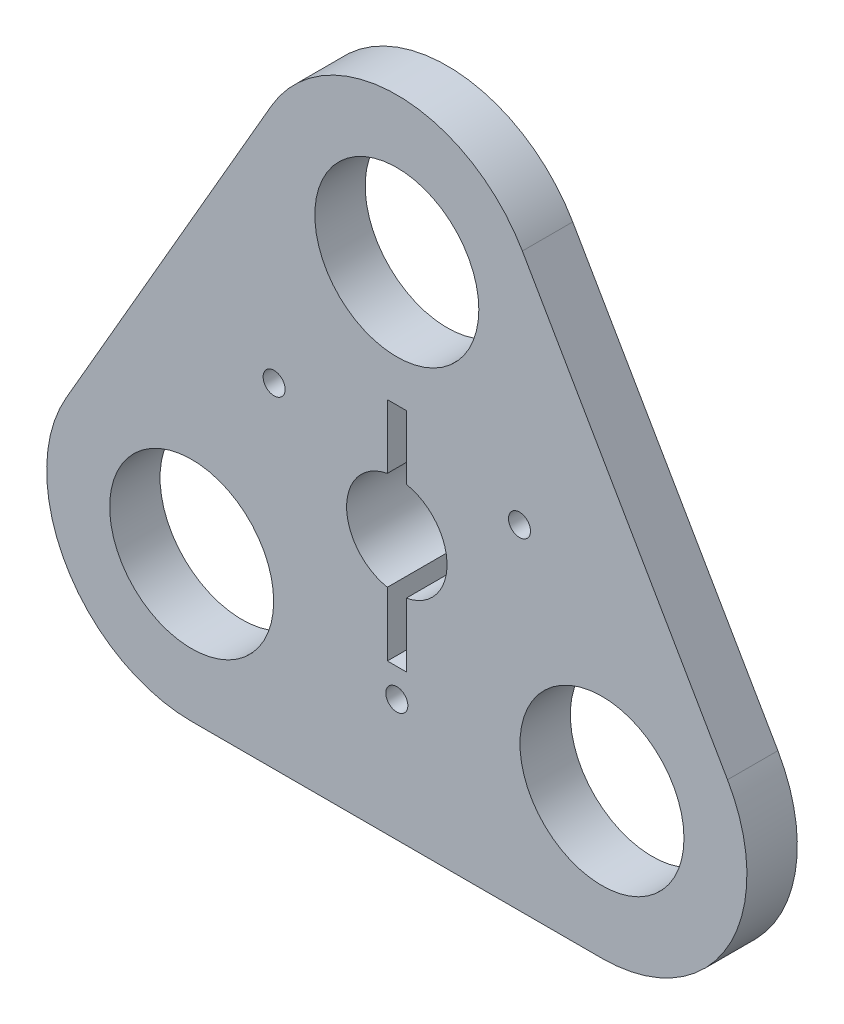
SolidWorks part; units mm, degrees
material "ABS"
ref_plane "Front Plane" through (0, 0, 0) normal (0, 0, 1) x (1, 0, 0)
ref_plane "Top Plane" through (0, 0, 0) normal (0, 1, 0) x (1, 0, 0)
ref_plane "Right Plane" through (0, 0, 0) normal (1, 0, 0) x (0, 0, -1)
sketch "Sketch1" plane through (0, 0, 0) normal (0, 0, 1) x (1, 0, 0)
  line L0 (0, 0) -> (0, 37.625) construction
  line L1 (0, 0) -> (32.5842, -18.8125) construction
  line L2 (0, 0) -> (-32.5842, -18.8125) construction
  line L3 (-19.9402, 49.1375) -> (-52.5244, -7.3)
  line L4 (-32.5842, -41.8375) -> (32.5842, -41.8375)
  line L5 (52.5244, -7.3) -> (19.9402, 49.1375)
  circle A0 centre (0, 0) radius 37.625 construction
  circle A1 centre (0, 0) radius 7.975
  circle A2 centre (0, 37.625) radius 13.025
  circle A3 centre (0, 37.625) radius 23.025
  circle A4 centre (32.5842, -18.8125) radius 13.025
  circle A5 centre (32.5842, -18.8125) radius 23.025
  circle A6 centre (-32.5842, -18.8125) radius 13.025
  circle A7 centre (-32.5842, -18.8125) radius 23.025
  dimension "carrier_diameter" = 75.25
  dimension "carrier_bearing_planet_OD" = 26.05
  dimension "carrier_shaft_diameter" = 15.95
  dimension "D1" = 120
  dimension "D2" = 120
  dimension "carrier_bearing_planet_radial_wall_thickness" = 10
extrude "Boss-Extrude1" add sketch "Sketch1" along normal mid plane 8 contours A3 A2 | A7 L4 A5 L5 A3 L3 A1 | A7 A6 | A5 A4 region at (-6.319, 14.0422, 0) region at (0, 59.9988, 0) region at (-26.7935, 2.7989, 0) region at (54.1956, -13.0217, 0)
sketch "Sketch5" plane through (0, 0, -4) normal (0, 0, -1) x (-1, 0, 0)
  line L0 (-5.8457, -25.875) -> (-25.3312, 7.875)
  line L2 (-19.4856, 18) -> (19.4856, 18)
  line L4 (25.3312, 7.875) -> (5.8457, -25.875)
  circle A0 centre (0, 0) radius 7.975 construction
  circle A1 centre (0, 0) radius 7.975
  circle A3 centre (0, 0) radius 22.5 construction
  circle A4 centre (0, -22.5) radius 1.75 construction
  arc A5 (-5.8457, -25.875) -> (5.8457, -25.875) centre (0, -22.5) ccw
  arc A6 (-19.4856, 18) -> (-25.3312, 7.875) centre (-19.4856, 11.25) ccw
  arc A7 (25.3312, 7.875) -> (19.4856, 18) centre (19.4856, 11.25) ccw
  point P14 (0, 0)
  dimension "D2" = 45
  dimension "D3" = 3.5
  dimension "D4" = 3
extrude "Boss-Extrude3" add sketch "Sketch5" along normal blind 4
chamfer "Chamfer2" distance 4 angle 45 6 edges at (0, -29.25, -4) (-15.5885, -9, -4) (15.5885, -9, -4) (-25.3312, 14.625, -4) (25.3312, 14.625, -4) (0, 18, -4)
sketch "Sketch2" plane through (0, 0, 4) normal (0, 0, 1) x (1, 0, 0)
  line L0 (1.5, 7.8327) -> (-1.5, 7.8327) construction
  line L1 (-1.5, 7.8327) -> (-1.5, 17.975)
  line L2 (-1.5, 17.975) -> (1.5, 17.975)
  line L3 (1.5, 17.975) -> (1.5, 7.8327)
  line L4 (0, 0) -> (0, 7.975) construction
  line L5 (0, 7.975) -> (0, 17.975) construction
  circle A0 centre (0, 0) radius 7.975 construction
  circle A1 centre (0, 0) radius 7.975
  circle M11 centre (0, 0) radius 7.975
  dimension "carrier_shaft_key_width" = 3
  dimension "carrier_shaft_key_height" = 10
extrude "Cut-Extrude1" cut sketch "Sketch2" against normal through all contours L3 L2 L1 M11 region at (0, 12.9513, 4)
sketch "Sketch3" plane through (0, 0, 4) normal (0, 0, 1) x (1, 0, 0)
  line L0 (0, 0) -> (0, 17.975) construction
  line L1 (-1.5, 17.975) -> (1.5, 17.975) construction
  line L2 (0, 0) -> (-19.4856, 11.25) construction
  circle A0 centre (0, 0) radius 22.5 construction
  circle A1 centre (-19.4856, 11.25) radius 1.75
  dimension "Screw_OD" = 3.5
  dimension "Screw_Circle_Diameter" = 45
  dimension "D1" = 60
extrude "Cut-Extrude2" cut sketch "Sketch3" against normal through all
pattern_circular "CirPattern2" count 3 over 360 about axis through (0, 0, 4) along (0, 0, -1) of "Cut-Extrude2"
pattern_circular "CirPattern3" count 2 over 360 about axis through (0, 0, 4) along (0, 0, -1) of "Cut-Extrude1"
equation "\"Bearing_PCD\"=75.25'Pitch circle diameter of bearing centres"
equation "\"Bearing_Thickness\"=8"
equation "\"Bearing_Wall_Thickness\"=10"
equation "\"Shaft_OD\"= 15.95"
equation "\"Key_Height\"=10"
equation "\"Key_Width\"=3"
equation "\"Bolt_Hole_OD\"=3.5"
equation "\"Bolt_Hole_PCD\"=45"
equation "\"Raised_Section_Thickness\"= 4"
equation "\"D1@Boss-Extrude3\"=\"Raised_Section_Thickness\""
equation "\"D1@Chamfer2\"=\"Raised_Section_Thickness\""
equation "\"Bearing_Diameter_Tolerance\"= 0.05"
equation "\"Bearing_OD\"=26"
equation "\"carrier_bearing_planet_OD@Sketch1\"=\"Bearing_OD\" + \"Bearing_Diameter_Tolerance\""
equation "\"carrier_shaft_diameter@Sketch1\"=\"Shaft_OD\""
equation "\"carrier_thickness@Boss-Extrude1\"=\"Bearing_Thickness\""
equation "\"carrier_shaft_key_width@Sketch2\"=\"Key_Width\""
equation "\"carrier_shaft_key_height@Sketch2\"=\"Key_Height\""
equation "\"Screw_OD@Sketch3\"= \"Bolt_Hole_OD\""
equation "\"Screw_Circle_Diameter@Sketch3\"= \"Bolt_Hole_PCD\""
equation "\"carrier_bearing_planet_radial_wall_thickness@Sketch1\"=\"Bearing_Wall_Thickness\""
equation "\"carrier_diameter@Sketch1\"=\"Bearing_PCD\""
equation "\"D2@Sketch5\"=\"Bolt_Hole_PCD\""
equation "\"D3@Sketch5\"=\"Bolt_Hole_OD\""
